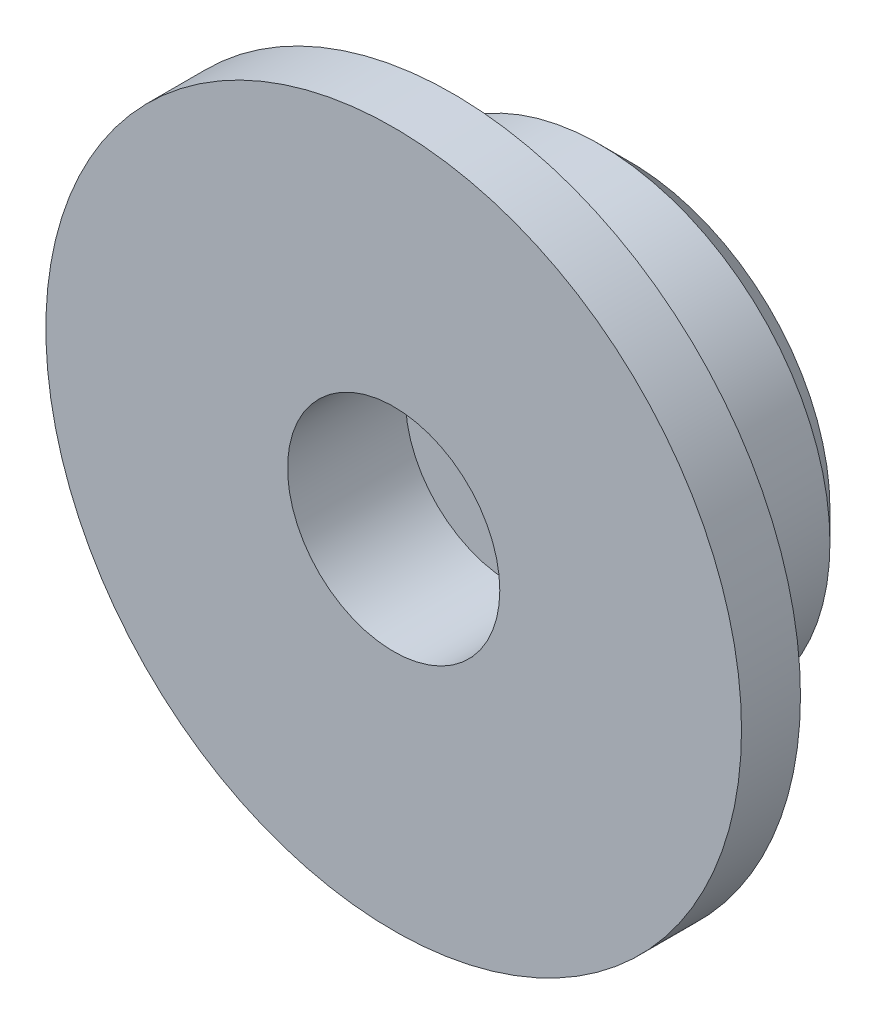
SolidWorks part; units mm, degrees
ref_plane "Спереди" through (0, 0, 0) normal (0, 0, 1) x (1, 0, 0)
ref_plane "Сверху" through (0, 0, 0) normal (0, 1, 0) x (1, 0, 0)
ref_plane "Справа" through (0, 0, 0) normal (1, 0, 0) x (0, 0, -1)
sketch "Эскиз1" plane through (0, 0, 0) normal (0, 0, 1) x (1, 0, 0)
  circle A1 centre (0, 0) radius 3.9
  dimension "D2" = 7.8
extrude "Бобышка-Вытянуть1" add sketch "Эскиз1" along normal blind 3
chamfer "Фаска1" distance 0.5 angle 45 1 edges at (3.9, 0, 0)
sketch "Эскиз4" plane through (0, 0, 3) normal (0, 0, 1) x (1, 0, 0)
  circle A2 centre (0, 0) radius 5.9
  circle A3 centre (0, 0) radius 5.9
  dimension "D1" = 2
extrude "Бобышка-Вытянуть2" add sketch "Эскиз4" along normal blind 1
sketch "Эскиз5" plane through (0, 0, 4) normal (0, 0, 1) x (1, 0, 0)
  circle A0 centre (0, 0) radius 1.8
  dimension "D1" = 3.6
extrude "Вырез-Вытянуть2" cut sketch "Эскиз5" against normal blind 2
